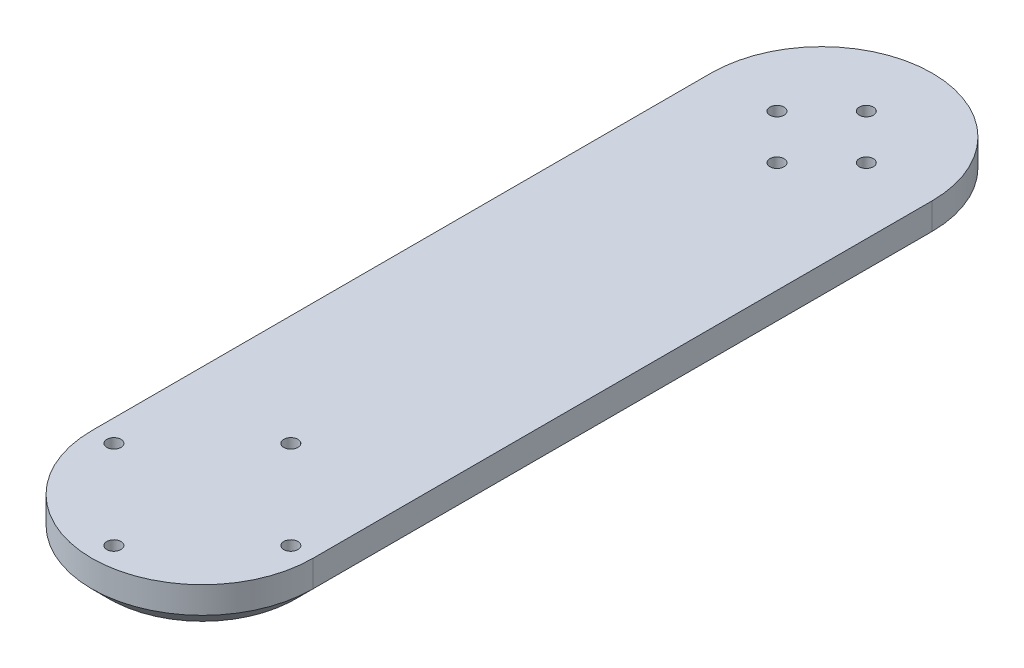
SolidWorks part; units mm, degrees
ref_plane "Front Plane" through (0, 0, 0) normal (0, 0, 1) x (1, 0, 0)
ref_plane "Top Plane" through (0, 0, 0) normal (0, 1, 0) x (1, 0, 0)
ref_plane "Right Plane" through (0, 0, 0) normal (1, 0, 0) x (0, 0, -1)
sketch "Sketch1" plane through (0, 0, 0) normal (0, 1, 0) x (1, 0, 0)
  line L0 (-25, 0) -> (-25, -140)
  line L1 (25, 0) -> (25, -140)
  line L3 (25, -140) -> (25, 0) construction
  arc A0 (25, 0) -> (-25, 0) centre (0, 0) ccw
  arc A4 (-25, -140) -> (25, -140) centre (0, -140) ccw
  arc A5 (-25, -140) -> (25, -140) centre (0, -140) ccw construction
  arc A6 (-25, -140) -> (25, -140) centre (0, -140) ccw construction
extrude "Boss-Extrude1" add sketch "Sketch1" along normal blind 10
sketch3d "3DSketch1"
  line L0 (0, 0, 0) -> (0, 20, 0) construction
  line L1 (0, 20, 0) -> (0, 20, 140) construction
  line L2 (0, 0, 140) -> (0, 20, 140) construction
  line L3 (-5, 20, 0) -> (5, 20, 0) construction
  line L4 (5, 20, 0) -> (5, 20, 140)
  line L5 (-5, 20, 140) -> (5, 20, 140) construction
  line L6 (-5, 20, 140) -> (-5, 20, 0)
  arc A0 (5, 20, 0) -> (-5, 20, 0) centre (0, 20, 0) ccw
  arc A1 (-5, 20, 140) -> (5, 20, 139.9906) centre (0, 20, 140) ccw
  point P8 (0, 20, 0)
  point P12 (0, 20, 140)
  point P13 (0, 25, 0)
  point P16 (0, 25, 140)
  dimension "D1" = 20
  dimension "D2" = 10
sketch "Sketch3" plane through (0, 0, 0) normal (0, -1, 0) x (1, 0, 0)
  circle A0 centre (10.0986, 0) radius 1.6 construction
  circle A1 centre (0, 10.0986) radius 1.6 construction
  circle A2 centre (0, -10.0986) radius 1.6 construction
  circle A3 centre (-10.0986, 0) radius 1.6 construction
  circle A4 centre (10.0986, 0) radius 1.6
  circle A5 centre (0, 10.0986) radius 1.6
  circle A6 centre (0, -10.0986) radius 1.6
  circle A7 centre (-10.0986, 0) radius 1.6
extrude "Cut-Extrude1" cut sketch "Sketch3" against normal through all
sketch "Sketch4" plane through (0, 0, 0) normal (0, -1, 0) x (1, 0, 0)
  circle A0 centre (0, 120) radius 1.6 construction
  circle A1 centre (20, 140) radius 1.6 construction
  circle A2 centre (0, 160) radius 1.6 construction
  circle A3 centre (-20, 140) radius 1.6 construction
  circle A4 centre (0, 120) radius 1.6
  circle A5 centre (20, 140) radius 1.6
  circle A6 centre (0, 160) radius 1.6
  circle A7 centre (-20, 140) radius 1.6
extrude "Cut-Extrude2" cut sketch "Sketch4" against normal through all
chamfer "Chamfer1" distance 4 angle 45 4 edges at (0, 0, 165) (25, 0, 70) (-25, 0, 70) (0, 0, -25)
